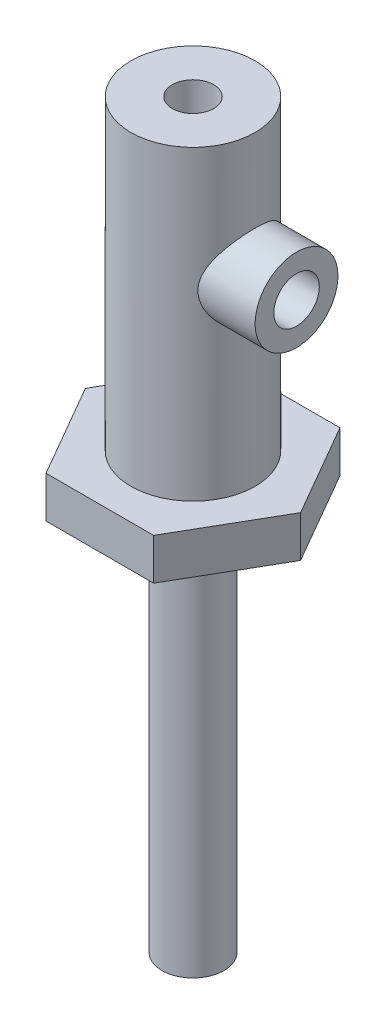
SolidWorks part; units mm, degrees
ref_plane "Front Plane" through (0, 0, 0) normal (0, 0, 1) x (1, 0, 0)
ref_plane "Top Plane" through (0, 0, 0) normal (0, 1, 0) x (1, 0, 0)
ref_plane "Right Plane" through (0, 0, 0) normal (1, 0, 0) x (0, 0, -1)
sketch "Sketch1" plane through (0, 0, 0) normal (0, 1, 0) x (1, 0, 0)
  circle A0 centre (0, 0) radius 3
  dimension "D1" = 6
extrude "Boss-Extrude1" add sketch "Sketch1" along normal blind 16.8
ref_plane "Plane1" through (0, 16.8, 0) normal (0, 1, 0) x (1, 0, 0)
ref_point "Point1"
sketch "Sketch2" plane through (0, 16.8, 0) normal (0, 1, 0) x (1, 0, 0)
  circle A0 centre (0, 0) radius 1
  dimension "D1" = 2
extrude "Cut-Extrude3" cut sketch "Sketch2" against normal blind 10.2
ref_plane "Plane2" through (0, 0, 0) normal (0, -1, 0) x (-1, 0, 0)
sketch "Sketch3" plane through (0, 0, 0) normal (0, -1, 0) x (-1, 0, 0)
  line L1 (5.1962, 0) -> (2.5981, 4.5)
  line L2 (2.5981, 4.5) -> (-2.5981, 4.5)
  line L3 (-2.5981, 4.5) -> (-5.1962, 0)
  line L4 (-5.1962, 0) -> (-2.5981, -4.5)
  line L5 (-2.5981, -4.5) -> (2.5981, -4.5)
  line L6 (2.5981, -4.5) -> (5.1962, 0)
  circle A0 centre (0, 0) radius 4.5 construction
extrude "Boss-Extrude2" add sketch "Sketch3" against normal blind 2
sketch "Sketch4" plane through (0, 0, 0) normal (0, -1, 0) x (-1, 0, 0)
  circle A0 centre (0, 0) radius 1.5
  dimension "D1" = 3
extrude "Boss-Extrude3" add sketch "Sketch4" along normal blind 19
ref_plane "Plane3" through (3, 0, 0) normal (1, 0, 0) x (0, 0, -1)
sketch "Sketch6" plane through (3, 0, 0) normal (1, 0, 0) x (0, 0, -1)
  line L0 (3.3, 16.8) -> (-3.3, 16.8) construction
  circle A0 centre (0, 10.8) radius 1.1
  circle A1 centre (0, 10.8) radius 2
  dimension "D2" = 2.2
  dimension "D3" = 4
  dimension "D1" = 6
extrude "Boss-Extrude4" add sketch "Sketch6" along normal blind 2 and the other way blind 1
ref_point "Point3"
sketch "Sketch7" plane through (3, 0, 0) normal (1, 0, 0) x (0, 0, -1)
  circle A0 centre (0, 10.8) radius 1.1
extrude "Cut-Extrude4" cut sketch "Sketch7" against normal blind 3
